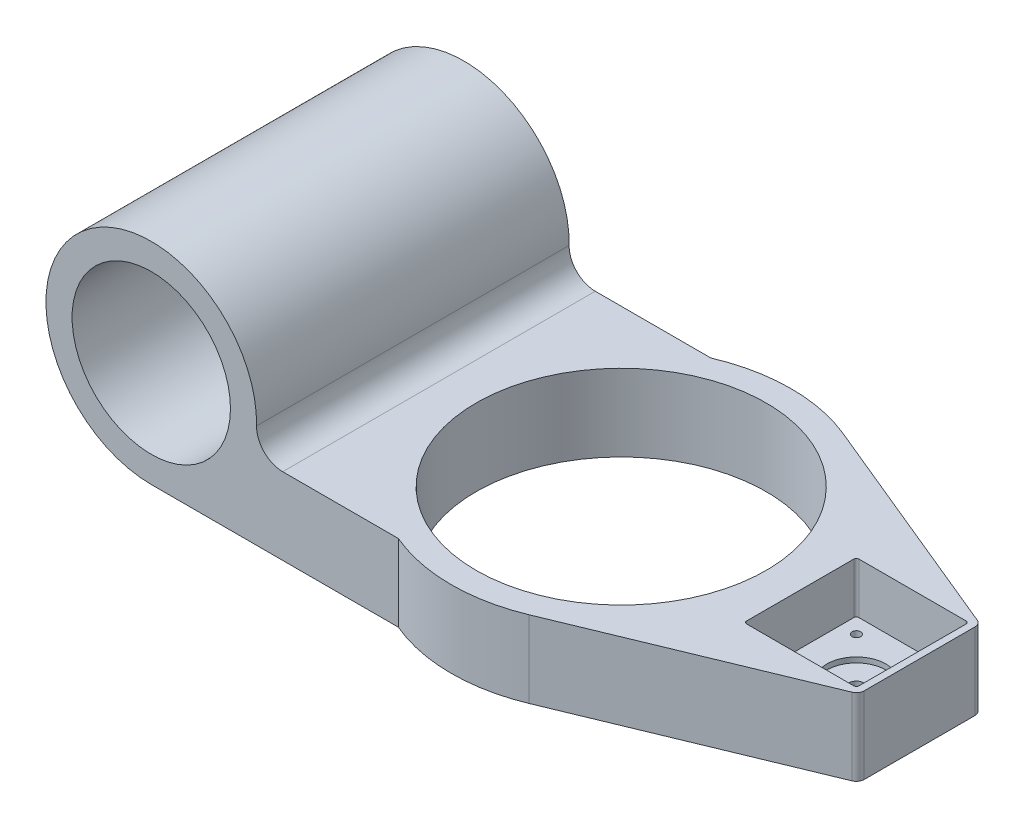
SolidWorks part; units mm, degrees
ref_plane "Front Plane" through (0, 0, 0) normal (0, 0, 1) x (1, 0, 0)
ref_plane "Top Plane" through (0, 0, 0) normal (0, 1, 0) x (1, 0, 0)
ref_plane "Right Plane" through (0, 0, 0) normal (1, 0, 0) x (0, 0, -1)
sketch "Sketch1" plane through (0, 0, 0) normal (0, 1, 0) x (1, 0, 0)
  line L0 (0, 0) -> (90, 0) construction
  line L1 (111.15, -24.15) -> (68.85, -24.15) construction
  line L2 (111.15, 21.15) -> (68.85, 21.15) construction
  line L3 (111.15, 21.15) -> (111.15, -21.15) construction
  line L4 (111.15, -21.15) -> (68.85, -21.15) construction
  line L5 (68.85, 21.15) -> (68.85, -21.15) construction
  line L6 (111.15, 21.15) -> (68.85, -21.15) construction
  line L7 (111.15, -21.15) -> (68.85, 21.15) construction
  line L8 (114.15, 21.15) -> (114.15, -21.15) construction
  line L9 (111.15, 24.15) -> (68.85, 24.15) construction
  line L10 (114.15, 24.15) -> (114.15, -24.15) construction
  line L11 (114.15, 24.15) -> (68.85, 24.15) construction
  line L12 (114.15, -24.15) -> (68.85, -24.15) construction
  line L13 (24.8266, -60.072) -> (112.2958, -23.9226)
  line L14 (112.2958, 23.9226) -> (24.8266, 60.072)
  line L15 (114.15, 21.15) -> (114.15, -21.15)
  circle A0 centre (0, 0) radius 55 construction
  circle A1 centre (0, 0) radius 55.5
  circle A2 centre (0, 0) radius 65 construction
  arc A3 (114.15, 21.15) -> (111.15, 24.15) centre (111.15, 21.15) ccw construction
  arc A4 (114.15, -21.15) -> (111.15, -24.15) centre (111.15, -21.15) cw construction
  arc A5 (114.15, -21.15) -> (112.2958, -23.9226) centre (111.15, -21.15) cw
  arc A6 (112.2958, 23.9226) -> (114.15, 21.15) centre (111.15, 21.15) cw
  arc A7 (24.8266, -60.072) -> (24.8266, 60.072) centre (0, 0) cw
  dimension "D1" = 110
  dimension "D3" = 130
  dimension "D7" = 3
  dimension "D4" = 90
  dimension "D5" = 42.3
  dimension "D2" = 0.5
  dimension "D6" = 3
extrude "Boss-Extrude1" add sketch "Sketch1" along normal blind 29.4
sketch "Sketch2" plane through (0, 29.4, 0) normal (0, 1, 0) x (1, 0, 0)
  line L0 (0, 0) -> (90, 0) construction
  line L2 (69.5, 21.5) -> (110.5, 21.5)
  line L3 (68.5, 20.5) -> (68.5, -20.5)
  line L4 (69.5, -21.5) -> (110.5, -21.5)
  line L5 (111.5, 20.5) -> (111.5, -20.5)
  line L6 (68.5, 21.5) -> (111.5, -21.5) construction
  line L7 (68.5, -21.5) -> (111.5, 21.5) construction
  arc A0 (69.5, 21.5) -> (68.5, 20.5) centre (69.5, 20.5) ccw
  arc A1 (110.5, 21.5) -> (111.5, 20.5) centre (110.5, 20.5) cw
  arc A2 (110.5, -21.5) -> (111.5, -20.5) centre (110.5, -20.5) ccw
  arc A3 (68.5, -20.5) -> (69.5, -21.5) centre (69.5, -20.5) ccw
  dimension "D3" = 1
  dimension "D1" = 90
  dimension "D2" = 43
extrude "Cut-Extrude1" cut sketch "Sketch2" against normal offset from surface (19.4 mm away) 10 up to face at (68.9267, 0, 0)
sketch "Sketch3" plane through (0, 10, 0) normal (0, 1, 0) x (1, 0, 0)
  line L0 (90, 0) -> (0, 0) construction
  line L1 (74.5, 15.5) -> (105.5, 15.5) construction
  line L2 (74.5, 15.5) -> (74.5, -15.5) construction
  line L3 (74.5, -15.5) -> (105.5, -15.5) construction
  line L4 (105.5, 15.5) -> (105.5, -15.5) construction
  line L5 (74.5, 15.5) -> (105.5, -15.5) construction
  line L6 (74.5, -15.5) -> (105.5, 15.5) construction
  circle A0 centre (74.5, -15.5) radius 1.65
  circle A1 centre (105.5, -15.5) radius 1.65
  circle A2 centre (105.5, 15.5) radius 1.65
  circle A3 centre (74.5, 15.5) radius 1.65
  circle A4 centre (90, 0) radius 2.8
  point P0 (90, 0)
  dimension "D2" = 3.3
  dimension "D4" = 5.6
  dimension "D1" = 90
  dimension "D3" = 31
extrude "Cut-Extrude2" cut sketch "Sketch3" against normal through all
sketch "Sketch4" plane through (0, 10, 0) normal (0, 1, 0) x (1, 0, 0)
  circle A0 centre (90, 0) radius 11.3
  dimension "D1" = 22.6
extrude "Cut-Extrude3" cut sketch "Sketch4" against normal blind 2
sketch "Sketch5" plane through (0, 0, 0) normal (0, -1, 0) x (1, 0, 0)
  circle A0 centre (74.5, 15.5) radius 3.3
  circle A1 centre (105.5, 15.5) radius 3.3
  circle A2 centre (74.5, -15.5) radius 3.3
  circle A3 centre (105.5, -15.5) radius 3.3
  dimension "D1" = 6.6
extrude "Cut-Extrude4" cut sketch "Sketch5" against normal blind 5
sketch "Sketch6" plane through (0, 0, 0) normal (0, 0, 1) x (1, 0, 0)
  line L0 (-65, 0) -> (24.8266, 0) construction
  circle A0 centre (-120, 40.3) radius 30.3
  circle A1 centre (-120, 40.3) radius 40.3
  dimension "D1" = 60.6
  dimension "D2" = 10
  dimension "D3" = 120
extrude "Boss-Extrude2" add sketch "Sketch6" along normal mid plane 119.6 separate body
sketch "Sketch7" plane through (0, 0, 59.8) normal (0, 0, 1) x (1, 0, 0)
  line L0 (-65, 29.4) -> (-65, 0)
  line L1 (-65, 0) -> (-120, 0)
  line L2 (-65, 29.4) -> (-81.2021, 29.4)
  circle A0 centre (-120, 40.3) radius 40.3 construction
  arc A1 (-120, 0) -> (-81.2021, 29.4) centre (-120, 40.3) ccw
extrude "Boss-Extrude3" add sketch "Sketch7" against normal up to surface (119.6 mm away) up to face at (-79.7, 40.3, -59.8)
sketch "Sketch8" plane through (0, 29.4, 0) normal (0, 1, 0) x (1, 0, 0)
  line L0 (-65, 59.8) -> (-65, -59.8) construction
  line L1 (-65, 59.8) -> (-65, -59.8)
  line L2 (-65, 59.8) -> (-25.4747, 59.8)
  line L3 (112.2958, 23.9226) -> (24.8266, 60.072)
  line L4 (24.8266, -60.072) -> (112.2958, -23.9226)
  line L5 (114.15, -21.15) -> (114.15, 21.15)
  line L9 (-65, -59.8) -> (-25.4747, -59.8)
  arc A3 (114.15, 21.15) -> (112.2958, 23.9226) centre (111.15, 21.15) ccw
  arc A4 (24.8266, 60.072) -> (24.8266, -60.072) centre (0, 0) ccw
  arc A5 (112.2958, -23.9226) -> (114.15, -21.15) centre (111.15, -21.15) ccw
  arc A7 (-25.4747, 59.8) -> (-25.4747, -59.8) centre (0, 0) ccw
  arc M17 (24.8266, 60.072) -> (24.8266, -60.072) centre (0, 0) ccw
  dimension "D1" = 0
extrude "Boss-Extrude4" add sketch "Sketch8" against normal up to surface (29.4 mm away) contours L1 L9 M17 | L2 L1 M17 region at (-54.1876, 29.4, -45.9003) region at (-54.1876, 29.4, 45.9003) up to face at (105.5, 0, 12.2)
fillet "Fillet1" radius 10 1 edges at (-81.2021, 29.4, 0)
